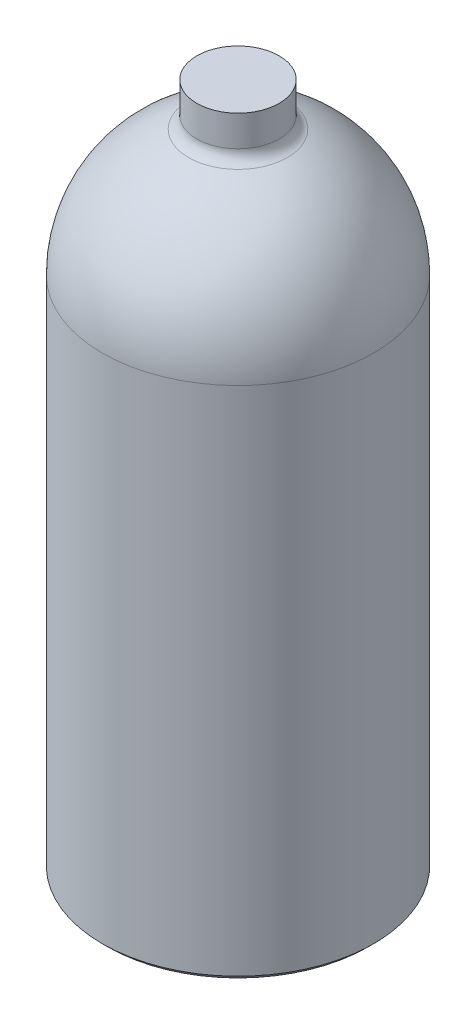
SolidWorks part; units mm, degrees
ref_plane "Front Plane" through (0, 0, 0) normal (0, 0, 1) x (1, 0, 0)
ref_plane "Top Plane" through (0, 0, 0) normal (0, 1, 0) x (1, 0, 0)
ref_plane "Right Plane" through (0, 0, 0) normal (1, 0, 0) x (0, 0, -1)
sketch "Sketch1" plane through (0, 0, 0) normal (0, 1, 0) x (1, 0, 0)
  circle A0 centre (0, 0) radius 66.675
  dimension "D1" = 133.35
extrude "Boss-Extrude1" add sketch "Sketch1" along normal mid plane 254.127
dome "Dome1" faces to dome 1 distance 66.675 reverse direction no elliptical dome no face at (0, 127.0635, 66.675) parameters "D1"=66.675
ref_plane "Plane1" through (0, 193.7385, 0) normal (0, 1, 0) x (1, 0, 0)
sketch "Sketch5" plane through (0, 193.7385, 0) normal (0, 1, 0) x (1, 0, 0)
  circle A0 centre (0, 0) radius 20.255
  dimension "D1" = 40.51
extrude "Boss-Extrude2" add sketch "Sketch5" along normal mid plane 33.02
chamfer "Chamfer1" distance 2.54 angle 45 1 edges at (0, -127.0635, 66.675)
fillet "Fillet1" radius 6.35 1 edges at (0, 190.5874, -20.255)
